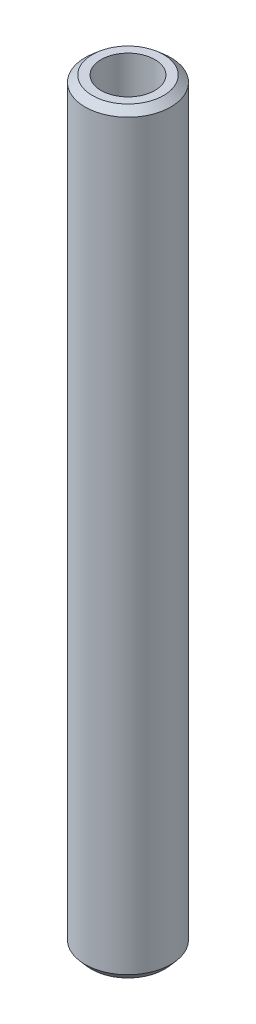
SolidWorks part; units mm, degrees
ref_plane "Front Plane" through (0, 0, 0) normal (0, 0, 1) x (1, 0, 0)
ref_plane "Top Plane" through (0, 0, 0) normal (0, 1, 0) x (1, 0, 0)
ref_plane "Right Plane" through (0, 0, 0) normal (1, 0, 0) x (0, 0, -1)
sketch "Sketch1" plane through (0, 0, 0) normal (0, 1, 0) x (1, 0, 0)
  circle A0 centre (0, 0) radius 17.5
  dimension "SHAFT_OD" = 35
extrude "Boss-Extrude1" add sketch "Sketch1" along normal blind 308.8651
sketch "Sketch2" plane through (0, 0, 0) normal (0, 1, 0) x (1, 0, 0)
  circle A0 centre (0, 0) radius 10.9666
  dimension "BORE_D" = 21.9332
extrude "Cut-Extrude1" cut sketch "Sketch2" along normal through all
chamfer "Chamfer1" distance 2.576 angle 49.158 2 edges at (0, 308.8651, 17.5) (0, 0, 17.5) first distance on face at (0, 308.8651, 17.5) first distance on face at (0, 0, 10.9666)
